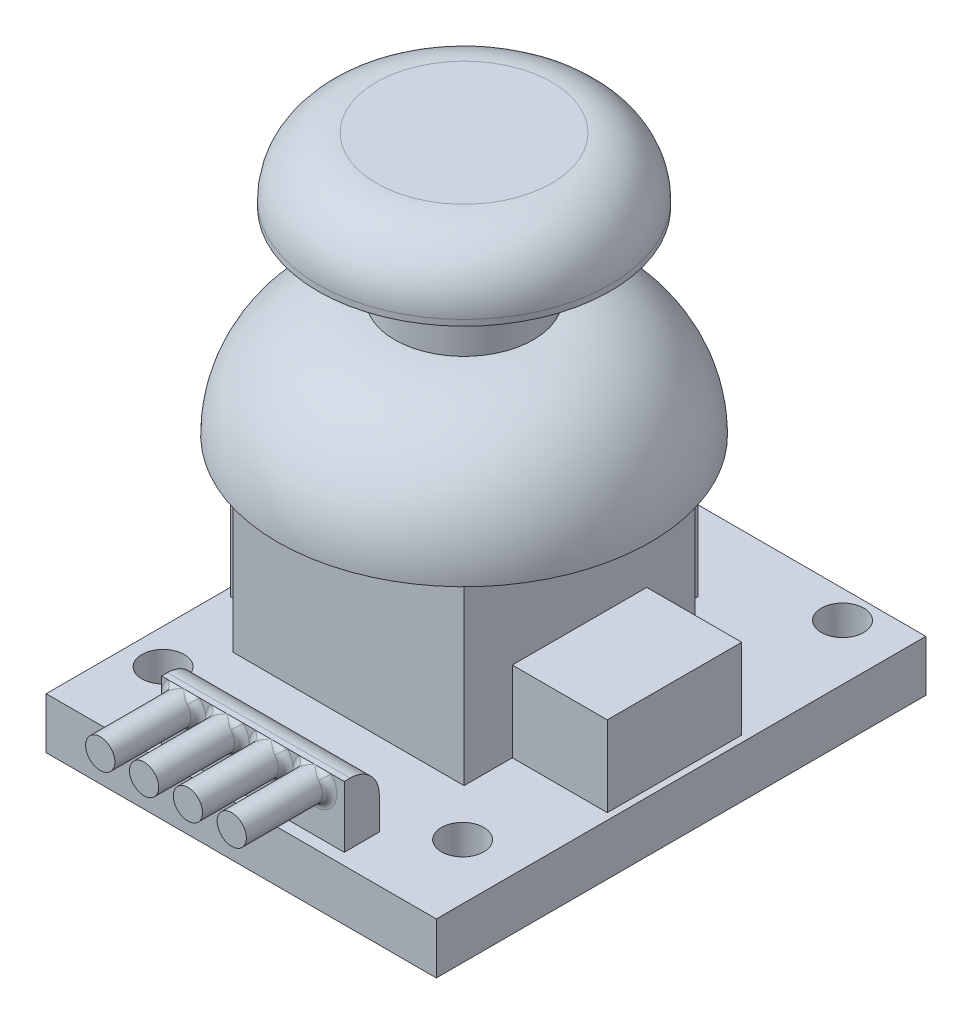
SolidWorks part; units mm, degrees
ref_plane "Спереди" through (0, 0, 0) normal (0, 0, 1) x (1, 0, 0)
ref_plane "Сверху" through (0, 0, 0) normal (0, 1, 0) x (1, 0, 0)
ref_plane "Справа" through (0, 0, 0) normal (1, 0, 0) x (0, 0, -1)
sketch "Sketch1" plane through (0, 0, 0) normal (0, 1, 0) x (1, 0, 0)
  line L1 (13.35, -16.75) -> (-13.35, -16.75)
  line L2 (13.35, -16.75) -> (13.35, 16.75)
  line L3 (13.35, 16.75) -> (-13.35, 16.75)
  line L4 (-13.35, -16.75) -> (-13.35, 16.75)
  line L5 (13.35, -16.75) -> (-13.35, 16.75) construction
  line L6 (13.35, 16.75) -> (-13.35, -16.75) construction
  point P0 (0, 0)
  dimension "D1" = 26.7
  dimension "D2" = 33.5
extrude "Boss-Extrude1" add sketch "Sketch1" along normal blind 3.5
sketch "Sketch2" plane through (0, 3.5, 0) normal (0, 1, 0) x (1, 0, 0)
  line L0 (13.35, 0) -> (-13.35, 0) construction
  line L1 (6.4, -7.9) -> (-9.4, -7.9)
  line L2 (6.4, -7.9) -> (6.4, 7.9)
  line L3 (6.4, 7.9) -> (-9.4, 7.9)
  line L4 (-9.4, -7.9) -> (-9.4, 7.9)
  line L5 (6.4, -7.9) -> (-9.4, 7.9) construction
  line L6 (6.4, 7.9) -> (-9.4, -7.9) construction
  line L7 (13.35, -16.75) -> (13.35, 16.75) construction
  line L8 (-13.35, 16.75) -> (-13.35, -16.75) construction
  point P0 (-1.5, 0)
  dimension "D1" = 15.8
  dimension "D2" = 1.5
extrude "Boss-Extrude2" add sketch "Sketch2" along normal blind 12.9
sketch "Sketch3" plane through (0, 16.4, 0) normal (0, 1, 0) x (1, 0, 0)
  circle A0 centre (0, 0) radius 1.9
  dimension "D1" = 3.8
extrude "Boss-Extrude3" add sketch "Sketch3" along normal blind 6.9
sketch "Sketch4" plane through (-9.4, 0, 0) normal (-1, 0, 0) x (0, 0, 1)
  line L0 (0, 16.4) -> (0, 3.5) construction
  line L1 (-7.9, 16.4) -> (7.9, 16.4) construction
  line L2 (-7.9, 3.5) -> (7.9, 3.5) construction
  line L4 (4.7, 3.5) -> (-4.7, 3.5)
  line L5 (4.7, 3.5) -> (4.7, 16.4)
  line L6 (4.7, 16.4) -> (-4.7, 16.4)
  line L7 (-4.7, 3.5) -> (-4.7, 16.4)
  line L8 (4.7, 3.5) -> (-4.7, 16.4) construction
  line L9 (4.7, 16.4) -> (-4.7, 3.5) construction
  point P6 (0, 9.95)
  dimension "D1" = 9.4
extrude "Boss-Extrude4" add sketch "Sketch4" along normal blind 3.4
sketch "Sketch5" plane through (0, 0, -7.9) normal (0, 0, -1) x (-1, 0, 0)
  line L0 (1.5, 16.4) -> (1.5, 3.5) construction
  line L1 (-6.4, 16.4) -> (9.4, 16.4) construction
  line L2 (-6.4, 3.5) -> (9.4, 3.5) construction
  line L4 (-3.2, 3.5) -> (6.2, 3.5)
  line L5 (-3.2, 3.5) -> (-3.2, 16.4)
  line L6 (-3.2, 16.4) -> (6.2, 16.4)
  line L7 (6.2, 3.5) -> (6.2, 16.4)
  line L8 (-3.2, 3.5) -> (6.2, 16.4) construction
  line L9 (-3.2, 16.4) -> (6.2, 3.5) construction
  point P6 (1.5, 9.95)
  dimension "D1" = 9.4
extrude "Boss-Extrude5" add sketch "Sketch5" along normal blind 3.4
sketch "Sketch6" plane through (6.4, 0, 0) normal (1, 0, 0) x (0, 0, -1)
  line L0 (0, 16.4) -> (0, 3.5) construction
  line L1 (-7.9, 16.4) -> (7.9, 16.4) construction
  line L2 (-7.9, 3.5) -> (7.9, 3.5) construction
  line L4 (-4.6, 9) -> (4.6, 9)
  line L5 (-4.6, 9) -> (-4.6, 3.5)
  line L6 (-4.6, 3.5) -> (4.6, 3.5)
  line L7 (4.6, 9) -> (4.6, 3.5)
  line L8 (-4.6, 9) -> (4.6, 3.5) construction
  line L9 (-4.6, 3.5) -> (4.6, 9) construction
  point P6 (0, 6.25)
  dimension "D1" = 9.2
  dimension "D2" = 5.5
extrude "Boss-Extrude6" add sketch "Sketch6" along normal blind 6.5
sketch "Sketch8" plane through (0, 16.4, 0) normal (0, 1, 0) x (1, 0, 0)
  line L0 (6.4, 7.9) -> (-9.4, -7.9) construction
  circle A0 centre (-1.5, 0) radius 12.75
  point P8 (-1.5, 0)
  dimension "D1" = 25.5
extrude "Boss-Extrude7" add sketch "Sketch8" along normal blind 8
fillet "Fillet1" radius 8 1 edges at (-1.5, 24.4, 12.75)
sketch "Sketch9" plane through (0, 24.4, 0) normal (0, 1, 0) x (1, 0, 0)
  circle A0 centre (-1.5, 0) radius 4.75
extrude "Boss-Extrude8" add sketch "Sketch9" along normal blind 5.5
sketch "Sketch10" plane through (0, 29.9, 0) normal (0, 1, 0) x (1, 0, 0)
  circle A0 centre (-1.5, 0) radius 10
  dimension "D1" = 20
extrude "Boss-Extrude9" add sketch "Sketch10" along normal blind 4.4
fillet "Fillet2" radius 4 1 edges at (-1.5, 34.3, 10)
sketch "Sketch11" plane through (0, 3.5, 0) normal (0, 1, 0) x (1, 0, 0)
  line L0 (-13.35, -14.75) -> (13.35, -14.75) construction
  line L1 (-13.35, 16.75) -> (-13.35, -16.75) construction
  line L2 (13.35, -16.75) -> (13.35, 16.75) construction
  line L3 (-13.35, -16.75) -> (13.35, -16.75) construction
  line L5 (6.25, -15.95) -> (-6.25, -15.95)
  line L6 (6.25, -15.95) -> (6.25, -13.55)
  line L7 (6.25, -13.55) -> (-6.25, -13.55)
  line L8 (-6.25, -15.95) -> (-6.25, -13.55)
  line L9 (6.25, -15.95) -> (-6.25, -13.55) construction
  line L10 (6.25, -13.55) -> (-6.25, -15.95) construction
  point P8 (0, -14.75)
  dimension "D1" = 2
  dimension "D2" = 2.4
  dimension "D3" = 12.5
extrude "Boss-Extrude10" add sketch "Sketch11" along normal blind 4.2
sketch "Sketch12" plane through (0, 0, 15.95) normal (0, 0, 1) x (1, 0, 0)
  line L0 (-6.25, 6.7) -> (6.25, 6.7) construction
  line L1 (-6.25, 7.7) -> (-6.25, 3.5) construction
  line L2 (6.25, 7.7) -> (6.25, 3.5) construction
  circle A0 centre (-4.75, 6.7) radius 1
  circle A1 centre (-1.75, 6.7) radius 1
  circle A2 centre (1.25, 6.7) radius 1
  circle A3 centre (4.25, 6.7) radius 1
  dimension "D1" = 1
  dimension "D2" = 3
  dimension "D3" = 3
  dimension "D4" = 3
  dimension "D5" = 1.5
extrude "Boss-Extrude11" add sketch "Sketch12" along normal blind 5.7
fillet "Fillet3" radius 2 1 edges at (0, 7.7, 13.55)
fillet "Fillet4" radius 0.5 4 edges at (5.25, 6.7, 15.95) (2.25, 6.7, 15.95) (-0.75, 6.7, 15.95) (-3.75, 6.7, 15.95)
sketch "Sketch13" plane through (0, 0, 0) normal (0, -1, 0) x (1, 0, 0)
  line L0 (9.55, -14.85) -> (-10.95, -14.85) construction
  line L1 (-10.95, -14.85) -> (-10.95, 11.15) construction
  line L2 (-10.95, 11.15) -> (9.55, 11.15) construction
  line L3 (9.55, 11.15) -> (9.55, -14.85) construction
  line L4 (13.35, -16.75) -> (-13.35, -16.75) construction
  line L5 (-13.35, -16.75) -> (-13.35, 16.75) construction
  circle A0 centre (9.55, -14.85) radius 1.45
  circle A1 centre (-10.95, -14.85) radius 1.45
  circle A2 centre (-10.95, 11.15) radius 1.45
  circle A3 centre (9.55, 11.15) radius 1.45
  dimension "D1" = 2.9
  dimension "D2" = 20.5
  dimension "D3" = 26
  dimension "D4" = 1.9
  dimension "D5" = 2.4
extrude "Cut-Extrude1" cut sketch "Sketch13" against normal up to next
